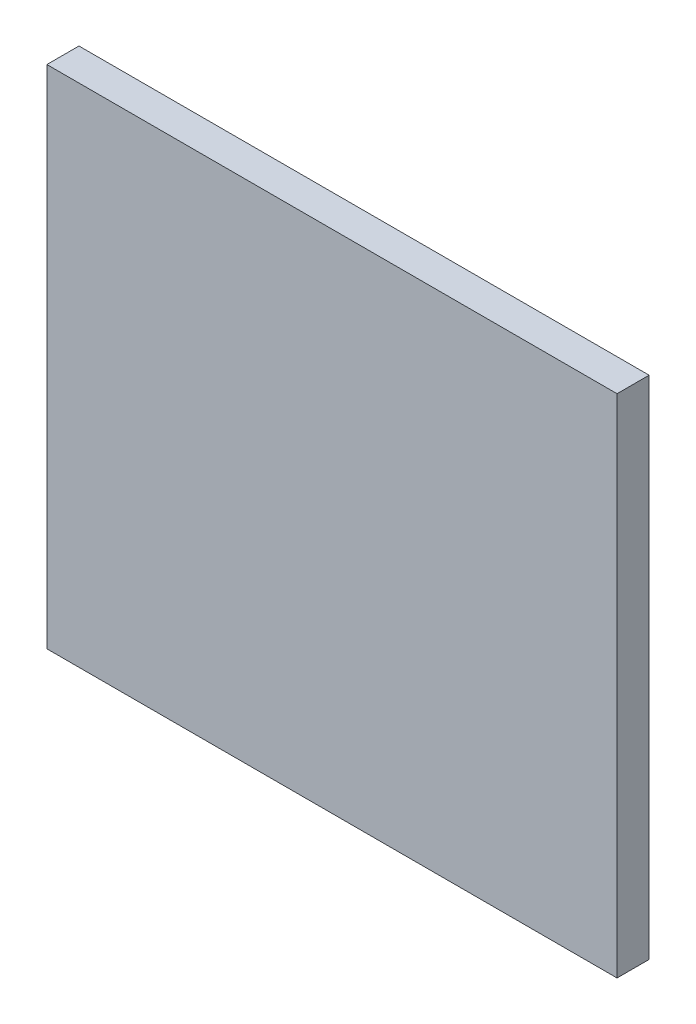
SolidWorks part; units mm, degrees
ref_plane "Front Plane" through (0, 0, 0) normal (0, 0, 1) x (1, 0, 0)
ref_plane "Top Plane" through (0, 0, 0) normal (0, 1, 0) x (1, 0, 0)
ref_plane "Right Plane" through (0, 0, 0) normal (1, 0, 0) x (0, 0, -1)
sketch "Sketch1" plane through (0, 0, 0) normal (0, 0, 1) x (1, 0, 0)
  line L1 (40, -35.5) -> (-40, -35.5)
  line L2 (40, -35.5) -> (40, 35.5)
  line L3 (40, 35.5) -> (-40, 35.5)
  line L4 (-40, -35.5) -> (-40, 35.5)
  line L5 (40, -35.5) -> (-40, 35.5) construction
  line L6 (40, 35.5) -> (-40, -35.5) construction
  point P0 (0, 0)
  dimension "D1" = 71
  dimension "D2" = 80
extrude "Boss-Extrude1" add sketch "Sketch1" along normal blind 4.5
